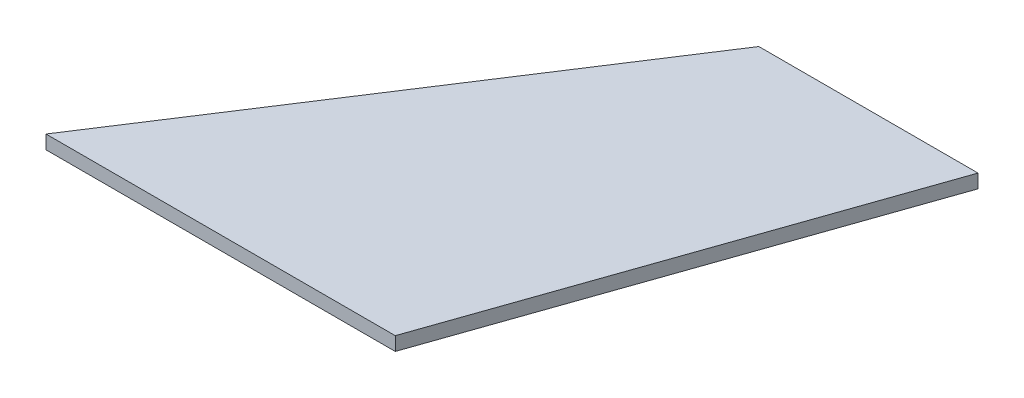
SolidWorks part; units mm, degrees
material "炭素鋼(普通)"
ref_plane "HOR" through (0, 0, 0) normal (0, 0, 1) x (1, 0, 0)
ref_plane "VERT" through (0, 0, 0) normal (0, 1, 0) x (1, 0, 0)
ref_plane "CTR" through (0, 0, 0) normal (1, 0, 0) x (0, 0, -1)
ref_axis "A_X" through (76.6329, 0, 0) along (-1, 0, 0)
ref_axis "A_Y" through (0, 1.1, 0) along (0, -1, 0)
ref_axis "A_Z" through (0, 0, 3.1555) along (0, 0, -1)
sketch3d "PNT_CG"
  point P0 (0, 0, 0)
sketch "Sketch1" plane through (0, 0, 0) normal (0, 1, 0) x (1, 0, 0)
  line L0 (0, 0) -> (51, 0)
  line L1 (-55, 0) -> (55, 0) construction
  line L2 (0, 0) -> (40.9837, 63.1094)
  line L3 (40.9837, 63.1094) -> (72.9837, 63.1094)
  line L4 (51, 0) -> (72.9837, 63.1094)
  dimension "D1" = 51
  dimension "D2" = 57
  dimension "D3" = 32
extrude "Boss-Extrude1" add sketch "Sketch1" along normal mid plane 2 contours L3 L4 L0 L2
